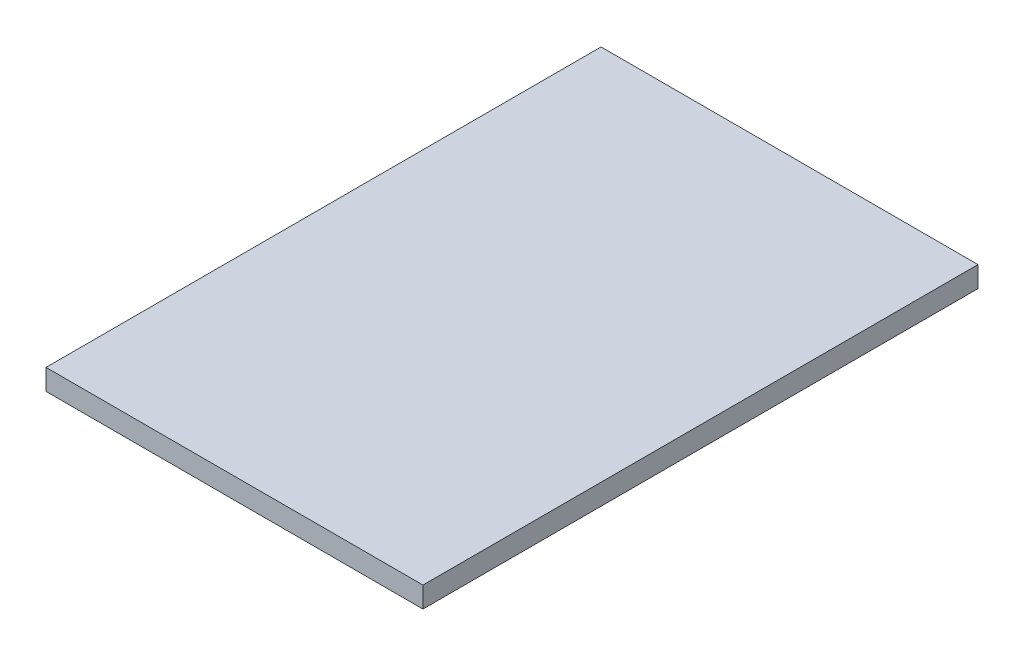
SolidWorks part; units mm, degrees
material "Perspex (TM) GS Acrylic Cast Sheet"
ref_plane "Front Plane" through (0, 0, 0) normal (0, 0, 1) x (1, 0, 0)
ref_plane "Top Plane" through (0, 0, 0) normal (0, 1, 0) x (1, 0, 0)
ref_plane "Right Plane" through (0, 0, 0) normal (1, 0, 0) x (0, 0, -1)
sketch "Sketch1" plane through (0, 0, 0) normal (0, 1, 0) x (1, 0, 0)
  line L1 (-81.5, -120) -> (81.5, -120)
  line L2 (-81.5, -120) -> (-81.5, 120)
  line L3 (-81.5, 120) -> (81.5, 120)
  line L4 (81.5, -120) -> (81.5, 120)
  line L5 (-81.5, -120) -> (81.5, 120) construction
  line L6 (-81.5, 120) -> (81.5, -120) construction
  point P0 (0, 0)
  dimension "D1" = 163
  dimension "D2" = 240
extrude "Boss-Extrude1" add sketch "Sketch1" along normal blind 9
sketch "Sketch2" plane through (0, 9, 0) normal (0, 1, 0) x (1, 0, 0)
  line L14 (-72.5, -111) -> (72.5, -111)
  line L15 (72.5, -111) -> (72.5, 111)
  line L16 (72.5, 111) -> (-72.5, 111)
  line L17 (-72.5, 111) -> (-72.5, -111)
  line L18 (-72.5, -111) -> (72.5, -111)
  line L19 (72.5, -111) -> (72.5, 111)
  line L20 (72.5, 111) -> (-72.5, 111)
  line L21 (-72.5, 111) -> (-72.5, -111)
  dimension "D1" = 9
equation "\"PCLength\"= 145mm'Length across I/O from PS to GPU"
equation "\"PCWidth\"= 340mm'Distance of longest part parallel to GPU(ussually GPU)"
equation "\"PCHeight\"= 180mm'Tallest point with mobo laying flat"
equation "\"WallThickness\"= 9mm'Thickness of each outer tank wall"
equation "\"ThermoBarrierThickness\"= 6mm'Thickness of barrier between hot side and cold side"
equation "\"HotSideGap\"= 36mm'Space in the hot side for a pump"
equation "\"PCClearance\"= 30mm'Clearance from top of tank to top of PC"
equation "\"RadiatorHeight\"= 275mm'Final Height from ground of radiators"
equation "\"AirflowGap\"= 25mm'Distance between radiators and tank for airflow"
equation "\"VolumeSubtraction\"= 230mm"
equation "\"D1@Sketch1\"=\"PCLength\" + (2 * \"WallThickness\")"
equation "\"D1@Boss-Extrude1\"=\"WallThickness\""
equation "\"D2@Sketch1\"=\"PCHeight\" + \"ThermoBarrierThickness\" + \"HotSideGap\" + (2 * \"WallThickness\")"
